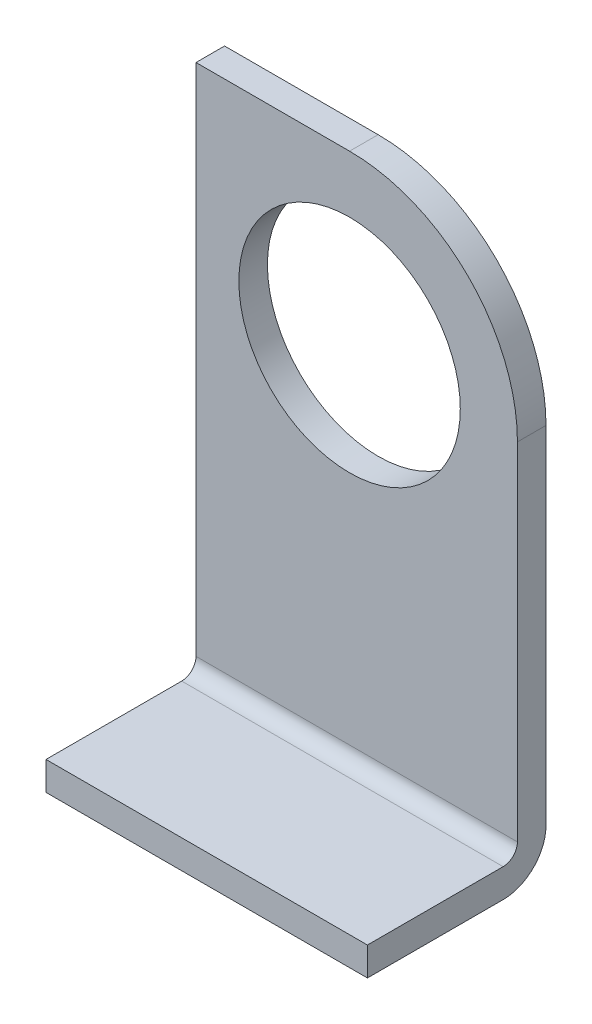
SolidWorks part; units mm, degrees
ref_plane "Front Plane" through (0, 0, 0) normal (0, 0, 1) x (1, 0, 0)
ref_plane "Top Plane" through (0, 0, 0) normal (0, 1, 0) x (1, 0, 0)
ref_plane "Right Plane" through (0, 0, 0) normal (1, 0, 0) x (0, 0, -1)
sketch "Sketch1" plane through (0, 0, 0) normal (0, 1, 0) x (1, 0, 0)
  line L1 (0, 0) -> (22.5, 0)
  line L2 (0, 0) -> (0, 12.5)
  line L3 (0, 12.5) -> (22.5, 12.5)
  line L4 (22.5, 0) -> (22.5, 12.5)
  dimension "D1" = 12.5
  dimension "D2" = 22.5
extrude "Boss-Extrude1" add sketch "Sketch1" along normal blind 2
sketch "Sketch2" plane through (0, 0, -12.5) normal (0, 0, -1) x (-1, 0, 0)
  line L1 (-22.5, 2) -> (0, 2)
  line L2 (-22.5, 2) -> (-22.5, 39)
  line L3 (-22.5, 39) -> (0, 39)
  line L4 (0, 2) -> (0, 39)
  dimension "D1" = 37
extrude "Boss-Extrude2" add sketch "Sketch2" against normal blind 2
fillet "Fillet1" radius 1 1 edges at (11.25, 2, -10.5)
fillet "Fillet2" radius 3 1 edges at (11.25, 0, -12.5)
sketch "Sketch5" plane through (0, 0, -12.5) normal (0, 0, -1) x (-1, 0, 0)
  line L1 (-22.5, 39) -> (-22.5, 3) construction
  line L2 (0, 39) -> (-22.5, 39) construction
  circle A0 centre (-10.75, 27.25) radius 7.75
  dimension "D1" = 4
  dimension "D2" = 4
  dimension "D3" = 15.5
extrude "Cut-Extrude1" cut sketch "Sketch5" against normal blind 2 contours A0
sketch "Sketch6" plane through (0, 0, -12.5) normal (0, 0, -1) x (-1, 0, 0)
  line L0 (-22.5, 39) -> (-22.5, 3) construction
  line L1 (0, 39) -> (-22.5, 39) construction
  arc A0 (-22.5, 27.25) -> (-10.75, 39) centre (-10.75, 27.25) cw
extrude "Cut-Extrude2" cut sketch "Sketch6" against normal blind 2 and the other way through all
